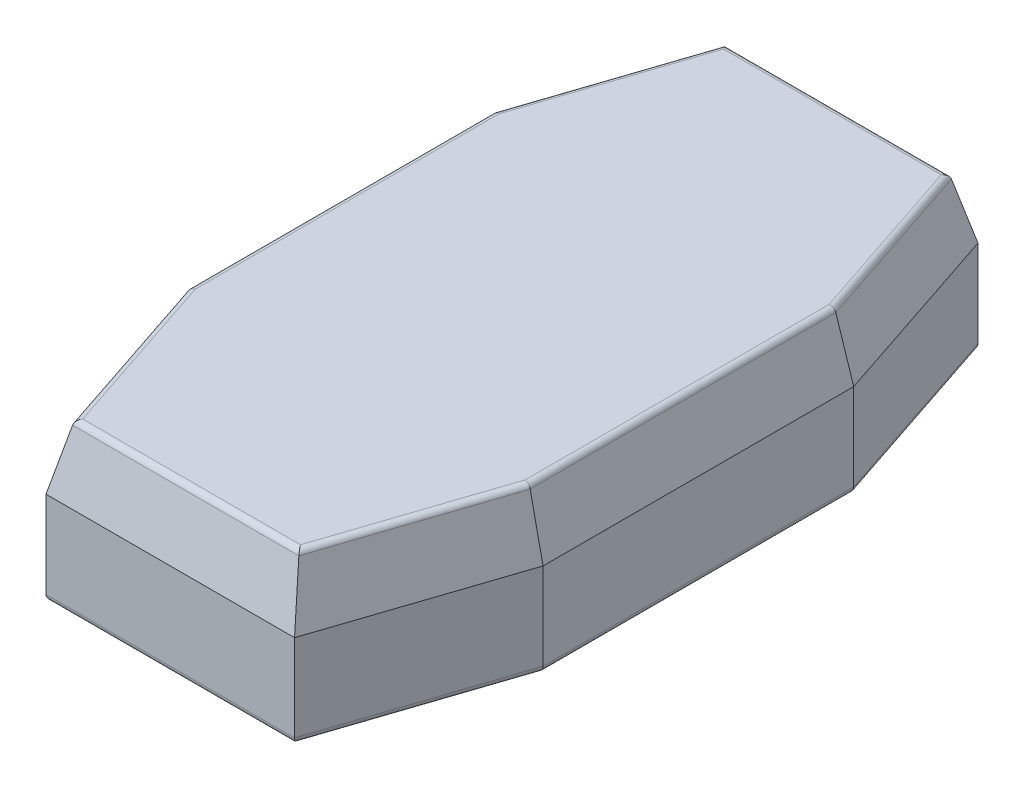
SolidWorks part; units mm, degrees
ref_plane "Front Plane" through (0, 0, 0) normal (0, 0, 1) x (1, 0, 0)
ref_plane "Top Plane" through (0, 0, 0) normal (0, 1, 0) x (1, 0, 0)
ref_plane "Right Plane" through (0, 0, 0) normal (1, 0, 0) x (0, 0, -1)
sketch "Sketch1" plane through (0, 0, 0) normal (0, 1, 0) x (1, 0, 0)
  line L0 (-7.62, 6.35) -> (-5.08, 13.97)
  line L1 (-5.08, 13.97) -> (5.08, 13.97)
  line L2 (-7.62, 6.35) -> (-7.62, -6.35)
  line L3 (-5.08, -13.97) -> (5.08, -13.97)
  line L4 (7.62, 6.35) -> (7.62, -6.35)
  line L5 (-7.62, 13.97) -> (7.62, -13.97) construction
  line L6 (-7.62, -13.97) -> (7.62, 13.97) construction
  line L7 (5.08, 13.97) -> (7.62, 6.35)
  line L8 (5.08, -13.97) -> (7.62, -6.35)
  line L9 (-7.62, -6.35) -> (-5.08, -13.97)
  point P0 (0, 0)
  dimension "D1" = 15.24
  dimension "D2" = 27.94
  dimension "D3" = 2.54
  dimension "D4" = 7.62
  dimension "D5" = 2.54
  dimension "D6" = 7.62
  dimension "D7" = 2.54
  dimension "D8" = 7.62
  dimension "D9" = 7.62
  dimension "D10" = 2.54
extrude "Boss-Extrude1" add sketch "Sketch1" along normal blind 2.54 draft 15
sketch "Stem" plane through (0, 0, 0) normal (0, -1, 0) x (1, 0, 0)
  line L1 (-0.5625, 2.075) -> (0.5625, 2.075)
  line L2 (-0.5625, 2.075) -> (-0.5625, -2.075)
  line L3 (-0.5625, -2.075) -> (0.5625, -2.075)
  line L4 (0.5625, 2.075) -> (0.5625, -2.075)
  line L5 (-0.5625, 2.075) -> (0.5625, -2.075) construction
  line L6 (-0.5625, -2.075) -> (0.5625, 2.075) construction
  line L7 (2.0625, 0.6625) -> (-2.0625, 0.6625)
  line L8 (2.0625, 0.6625) -> (2.0625, -0.6625)
  line L9 (2.0625, -0.6625) -> (-2.0625, -0.6625)
  line L10 (-2.0625, 0.6625) -> (-2.0625, -0.6625)
  line L11 (2.0625, 0.6625) -> (-2.0625, -0.6625) construction
  line L12 (2.0625, -0.6625) -> (-2.0625, 0.6625) construction
  line L13 (-2.5, 2.375) -> (2.5, 2.375)
  line L14 (-3, 1.875) -> (-3, -1.875)
  line L15 (-2.5, -2.375) -> (2.5, -2.375)
  line L16 (3, 1.875) -> (3, -1.875)
  line L17 (-3, 2.375) -> (3, -2.375) construction
  line L18 (-3, -2.375) -> (3, 2.375) construction
  arc A0 (-3, -1.875) -> (-2.5, -2.375) centre (-2.5, -1.875) ccw
  arc A1 (-2.5, 2.375) -> (-3, 1.875) centre (-2.5, 1.875) ccw
  arc A2 (2.5, -2.375) -> (3, -1.875) centre (2.5, -1.875) ccw
  arc A3 (2.5, 2.375) -> (3, 1.875) centre (2.5, 1.875) cw
  point P0 (0, 0)
  point P6 (0, 0)
  point P11 (0, 0)
  dimension "D7" = 0.5
  dimension "D1" = 4.15
  dimension "D2" = 1.125
  dimension "D3" = 1.325
  dimension "D4" = 4.125
  dimension "D5" = 4.75
  dimension "D6" = 6
extrude "Boss-Extrude2" add sketch "Stem" along normal blind 3.8 contours A3 L13 A1 L14 A0 L15 A2 L16 L10 L7 L2 L1 L4 L8 L9 L3 region at (0, 0, 2.2985)
fillet "Fillet2" radius 0.1 8 edges at (-2.8536, -3.8, -2.2286) (-3, -3.8, 0) (-2.8536, -3.8, 2.2286) (0, -3.8, 2.375) (2.8536, -3.8, 2.2286) (3, -3.8, 0) (2.8536, -3.8, -2.2286) (0, -3.8, -2.375)
chamfer "Chamfer1" distance 0.2 angle 45 11 edges at (-0.5625, -3.8, -1.3688) (-1.3125, -3.8, -0.6625) (-2.0625, -3.8, 0) (0.5625, -3.8, -1.3688) (1.3125, -3.8, -0.6625) (2.0625, -3.8, 0) (1.3125, -3.8, 0.6625) (0.5625, -3.8, 1.3687) (0, -3.8, 2.075) (-0.5625, -3.8, 1.3687) (-1.3125, -3.8, 0.6625)
sketch "Sketch3" plane through (0, 0, 0) normal (0, -1, 0) x (1, 0, 0)
  line L0 (-7.62, 6.35) -> (-7.62, -6.35)
  line L1 (-7.62, -6.35) -> (-5.08, -13.97)
  line L2 (-5.08, -13.97) -> (5.08, -13.97)
  line L3 (5.08, -13.97) -> (7.62, -6.35)
  line L4 (7.62, -6.35) -> (7.62, 6.35)
  line L5 (7.62, 6.35) -> (5.08, 13.97)
  line L6 (5.08, 13.97) -> (-5.08, 13.97)
  line L7 (-5.08, 13.97) -> (-7.62, 6.35)
  line L44 (-6.35, -6.1439) -> (-4.1646, -12.7)
  line L45 (-4.1646, -12.7) -> (4.1646, -12.7)
  line L46 (4.1646, -12.7) -> (6.35, -6.1439)
  line L47 (6.35, -6.1439) -> (6.35, 6.1439)
  line L48 (6.35, 6.1439) -> (4.1646, 12.7)
  line L49 (4.1646, 12.7) -> (-4.1646, 12.7)
  line L50 (-4.1646, 12.7) -> (-6.35, 6.1439)
  line L51 (-6.35, 6.1439) -> (-6.35, -6.1439)
  line L52 (-6.35, -6.1439) -> (-4.1646, -12.7)
  line L53 (-4.1646, -12.7) -> (4.1646, -12.7)
  line L54 (4.1646, -12.7) -> (6.35, -6.1439)
  line L55 (6.35, -6.1439) -> (6.35, 6.1439)
  line L56 (6.35, 6.1439) -> (4.1646, 12.7)
  line L57 (4.1646, 12.7) -> (-4.1646, 12.7)
  line L58 (-4.1646, 12.7) -> (-6.35, 6.1439)
  line L59 (-6.35, 6.1439) -> (-6.35, -6.1439)
  dimension "D1" = 1.27
extrude "Boss-Extrude3" add sketch "Sketch3" along normal blind 3.8
fillet "Fillet3" radius 0.25 16 edges at (0, -3.8, -12.7) (5.2573, -3.8, -9.422) (6.35, -3.8, 0) (5.2573, -3.8, 9.422) (0, -3.8, 12.7) (-5.2573, -3.8, 9.422) (-6.35, -3.8, 0) (-5.2573, -3.8, -9.422) (0, -3.8, 13.97) (6.35, -3.8, 10.16) (7.62, -3.8, 0) (6.35, -3.8, -10.16) (0, -3.8, -13.97) (-6.35, -3.8, -10.16) (-7.62, -3.8, 0) (-6.35, -3.8, 10.16)
fillet "Fillet5" radius 0.5 16 edges at (0, 0, 2.375) (-2.8536, 0, 2.2286) (-3, 0, 0) (-2.8536, 0, -2.2286) (0, 0, -2.375) (2.8536, 0, -2.2286) (3, 0, 0) (2.8536, 0, 2.2286) (-5.2573, 0, 9.422) (0, 0, 12.7) (5.2573, 0, 9.422) (6.35, 0, 0) (5.2573, 0, -9.422) (0, 0, -12.7) (-5.2573, 0, -9.422) (-6.35, 0, 0)
fillet "Fillet6" radius 0.1 12 edges at (-1.3125, 0, 0.6625) (-0.5625, 0, 1.3687) (0, 0, 2.075) (0.5625, 0, 1.3687) (1.3125, 0, 0.6625) (2.0625, 0, 0) (1.3125, 0, -0.6625) (0.5625, 0, -1.3688) (0, 0, -2.075) (-0.5625, 0, -1.3688) (-1.3125, 0, -0.6625) (-2.0625, 0, 0)
fillet "Fillet7" radius 0.25 8 edges at (5.7644, 2.54, -9.7645) (6.9394, 2.54, 0) (5.7644, 2.54, 9.7645) (0, 2.54, 13.2894) (-5.7644, 2.54, 9.7645) (-6.9394, 2.54, 0) (-5.7644, 2.54, -9.7645) (0, 2.54, -13.2894)
